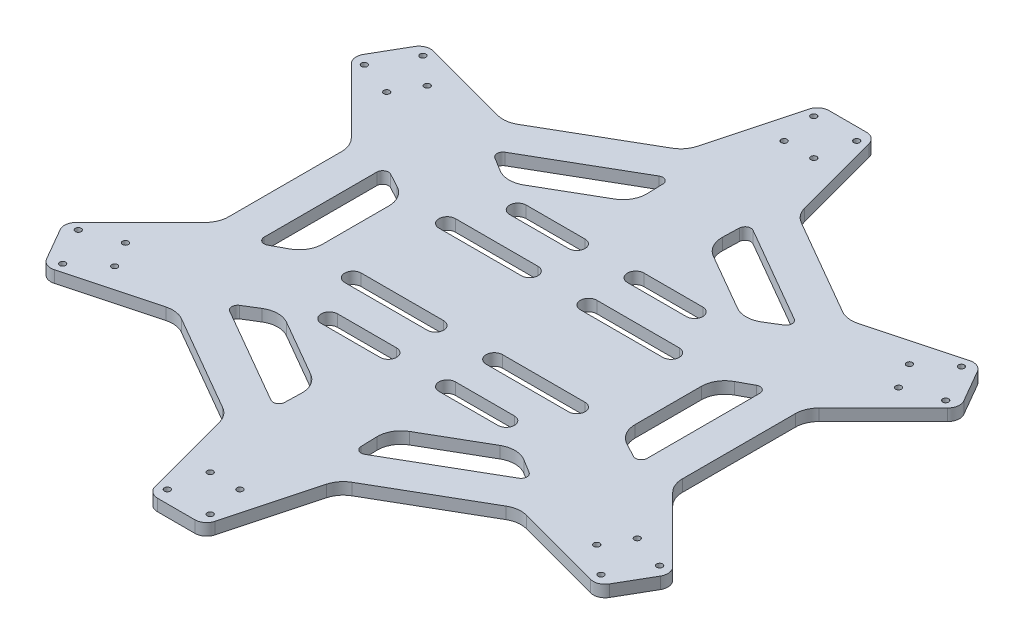
SolidWorks part; units mm, degrees
ref_plane "Front Plane" through (0, 0, 0) normal (0, 0, 1) x (1, 0, 0)
ref_plane "Top Plane" through (0, 0, 0) normal (0, 1, 0) x (1, 0, 0)
ref_plane "Right Plane" through (0, 0, 0) normal (1, 0, 0) x (0, 0, -1)
sketch "Sketch1" plane through (0, 0, 0) normal (0, 1, 0) x (1, 0, 0)
  line L1 (-82.2724, 142.5) -> (-164.5448, 0)
  line L2 (-164.5448, 0) -> (-82.2724, -142.5)
  line L3 (-82.2724, -142.5) -> (82.2724, -142.5)
  line L4 (82.2724, -142.5) -> (164.5448, 0)
  line L5 (164.5448, 0) -> (82.2724, 142.5)
  line L6 (82.2724, 142.5) -> (-82.2724, 142.5)
  circle A0 centre (0, 0) radius 142.5 construction
  dimension "D1" = 285
extrude "Boss-Extrude1" add sketch "Sketch1" along normal blind 5
sketch "Sketch3" plane through (0, 5, 0) normal (0, 1, 0) x (1, 0, 0)
  line L0 (0, 0) -> (0, 142.5) construction
  line L1 (82.2724, 142.5) -> (-82.2724, 142.5) construction
  line L2 (-11.75, 142.5) -> (11.75, 142.5) construction
  line L3 (0, 0) -> (123.4086, 71.25) construction
  line L4 (164.5448, 0) -> (82.2724, 142.5) construction
  line L5 (117.5336, 81.4258) -> (129.2836, 61.0742) construction
  line L6 (11.75, 142.5) -> (23.8194, 97.4564)
  line L7 (23.8194, 97.4564) -> (72.49, 69.3564)
  line L8 (72.49, 69.3564) -> (117.5336, 81.4258)
  line L9 (11.75, 142.5) -> (82.2724, 142.5)
  line L10 (82.2724, 142.5) -> (117.5336, 81.4258)
  line L11 (11.75, 142.5) -> (117.5336, 81.4258) construction
  line L12 (-9.1, 137.2) -> (9.1, 137.2) construction
  line L13 (-6.3, 121.8) -> (6.3, 121.8) construction
  line L14 (16.3194, 84.466) -> (64.99, 56.366)
  line L15 (64.99, 56.366) -> (50.4752, 47.4256)
  line L16 (50.4752, 47.4256) -> (15.8342, 67.4256)
  line L17 (15.8342, 67.4256) -> (16.3194, 84.466)
  line L18 (23.8194, 97.4564) -> (16.3194, 84.466) construction
  line L19 (72.49, 69.3564) -> (64.99, 56.366) construction
  line L20 (40.6547, 70.416) -> (33.1547, 57.4256) construction
  circle A0 centre (9.1, 137.2) radius 1.25
  circle A1 centre (-9.1, 137.2) radius 1.25
  circle A2 centre (-6.3, 121.8) radius 1.25
  circle A3 centre (6.3, 121.8) radius 1.25
  point P7 (0, 142.5)
  point P13 (123.4086, 71.25)
  point P26 (0, 121.8)
  point P27 (0, 137.2)
  dimension "D4" = 2.5
  dimension "D1" = 23.5
  dimension "D2" = 23.5
  dimension "D3" = 56.2
  dimension "D5" = 5.3
  dimension "D6" = 20.7
  dimension "D7" = 18.2
  dimension "D8" = 12.6
  dimension "D9" = 40
  dimension "D10" = 15
  dimension "D11" = 15
extrude "Cut-Extrude1" cut sketch "Sketch3" against normal through all
fillet "Fillet3" radius 2.5 2 edges at (64.99, 2.5, -56.366) (16.3194, 2.5, -84.466)
fillet "Fillet4" radius 10 2 edges at (50.4752, 2.5, -47.4256) (15.8342, 2.5, -67.4256)
ref_point "Point2"
ref_axis "Axis2" through (0, 0, 0) along (0, 1, 0)
pattern_circular "CirPattern4" count 6 over 360 about axis through (0, 0, 0) along (0, 1, 0) of "Cut-Extrude1", "Fillet3", "Fillet4"
fillet "Fillet1" radius 10 12 edges at (72.49, 2.5, -69.3564) (23.8194, 2.5, -97.4564) (96.3094, 2.5, -28.1) (96.3094, 2.5, 28.1) (72.49, 2.5, 69.3564) (23.8194, 2.5, 97.4564) (-23.8194, 2.5, 97.4564) (-72.49, 2.5, 69.3564) (-96.3094, 2.5, 28.1) (-96.3094, 2.5, -28.1) (-72.49, 2.5, -69.3564) (-23.8194, 2.5, -97.4564)
fillet "Fillet2" radius 5 12 edges at (11.75, 2.5, -142.5) (117.5336, 2.5, -81.4258) (-117.5336, 2.5, -81.4258) (-11.75, 2.5, -142.5) (-129.2836, 2.5, -61.0742) (-129.2836, 2.5, 61.0742) (-117.5336, 2.5, 81.4258) (-11.75, 2.5, 142.5) (11.75, 2.5, 142.5) (117.5336, 2.5, 81.4258) (129.2836, 2.5, 61.0742) (129.2836, 2.5, -61.0742)
ref_axis "Axis3" through (0, 0, 0) along (0, 0, -1)
ref_axis "Axis4" through (0, 0, 0) along (1, 0, 0)
sketch "Sketch6" plane through (0, 5, 0) normal (0, 1, 0) x (1, 0, 0)
  line L0 (0, 0) -> (0, 40) construction
  line L1 (0, 0) -> (0, 162.2653) construction
  line L2 (0, 40) -> (25, 40) construction
  line L3 (0, 20) -> (30, 20) construction
  line L4 (12.5, 40) -> (37.5, 40) construction
  line L5 (12.5, 43.5) -> (37.5, 43.5)
  line L6 (12.5, 36.5) -> (37.5, 36.5)
  line L7 (12.5, 20) -> (47.5, 20) construction
  line L8 (12.5, 23.5) -> (47.5, 23.5)
  line L9 (12.5, 16.5) -> (47.5, 16.5)
  line L10 (-12.5, 20) -> (-47.5, 20) construction
  line L11 (-12.5, 23.5) -> (-47.5, 23.5)
  line L12 (-12.5, 16.5) -> (-47.5, 16.5)
  line L13 (-12.5, 40) -> (-37.5, 40) construction
  line L14 (-12.5, 43.5) -> (-37.5, 43.5)
  line L15 (-12.5, 36.5) -> (-37.5, 36.5)
  arc A0 (12.5, 43.5) -> (12.5, 36.5) centre (12.5, 40) ccw
  arc A1 (37.5, 36.5) -> (37.5, 43.5) centre (37.5, 40) ccw
  arc A2 (12.5, 23.5) -> (12.5, 16.5) centre (12.5, 20) ccw
  arc A3 (47.5, 16.5) -> (47.5, 23.5) centre (47.5, 20) ccw
  arc A4 (-12.5, 23.5) -> (-12.5, 16.5) centre (-12.5, 20) cw
  arc A5 (-47.5, 16.5) -> (-47.5, 23.5) centre (-47.5, 20) cw
  arc A6 (-12.5, 43.5) -> (-12.5, 36.5) centre (-12.5, 40) cw
  arc A7 (-37.5, 36.5) -> (-37.5, 43.5) centre (-37.5, 40) cw
  point P10 (25, 40)
  point P17 (30, 20)
  point P24 (-30, 20)
  point P31 (-25, 40)
  dimension "D4" = 17.5
  dimension "D1" = 40
  dimension "D2" = 12.5
  dimension "D3" = 3.5
  dimension "D5" = 3.5
extrude "Cut-Extrude2" cut sketch "Sketch6" against normal through all
ref_plane "Plane1" through (0, 0, 0) normal (0, 0, 1) x (1, 0, 0)
mirror "Mirror1" about plane through (0, 0, 0) normal (0, 0, 1) of "Cut-Extrude2"
